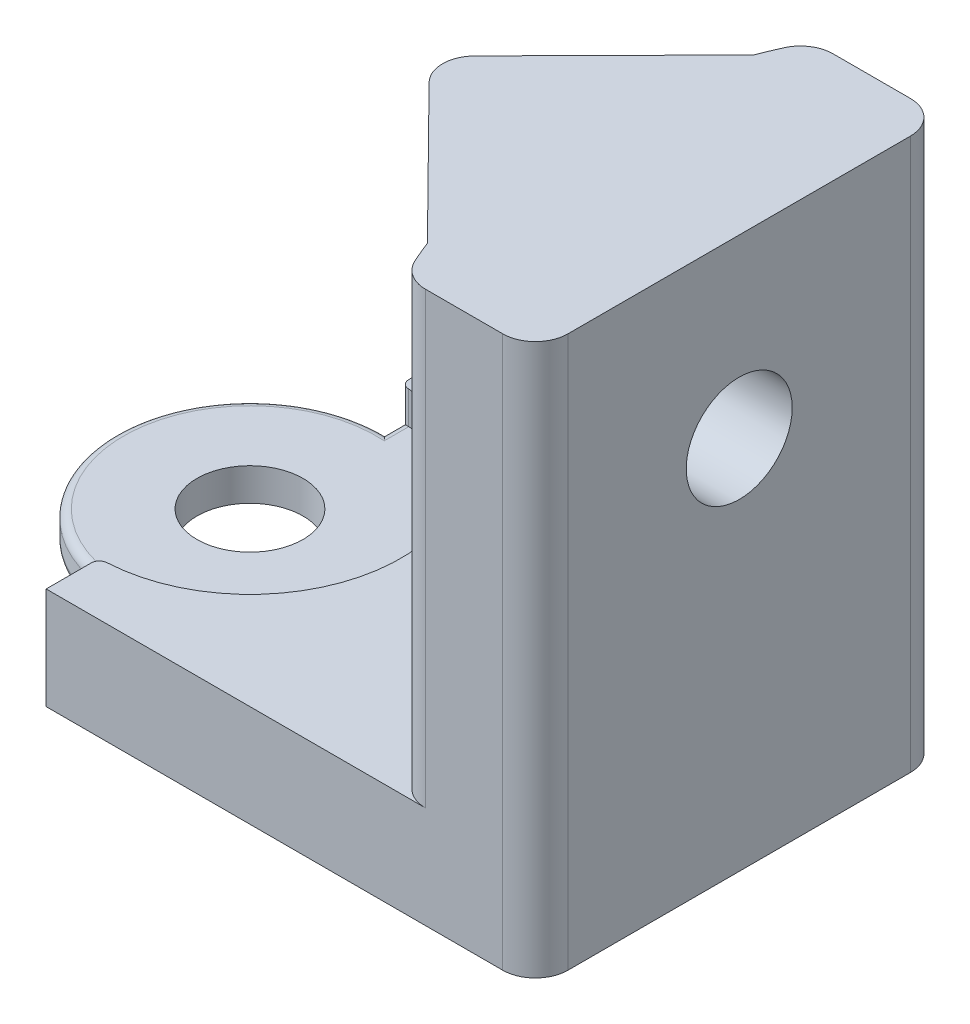
SolidWorks part; units mm, degrees
ref_plane "Front Plane" through (0, 0, 0) normal (0, 0, 1) x (1, 0, 0)
ref_plane "Top Plane" through (0, 0, 0) normal (0, 1, 0) x (1, 0, 0)
ref_plane "Right Plane" through (0, 0, 0) normal (1, 0, 0) x (0, 0, -1)
sketch "Sketch1" plane through (0, 0, 0) normal (0, 1, 0) x (1, 0, 0)
  line L0 (30, -12.5) -> (0, -12.5)
  line L1 (30, -12.5) -> (30, 12.5)
  line L2 (0, -12.5) -> (0, 12.5)
  line L3 (30, 12.5) -> (0, 12.5)
  line L4 (30, -12.5) -> (0, 12.5) construction
  line L5 (0, -12.5) -> (30, 12.5) construction
  line L6 (22, 12.5) -> (22, -12.5) construction
  circle A0 centre (0, 0) radius 3.25
  circle A1 centre (0, 0) radius 8.25
  arc A3 (0, -9.25) -> (0, 9.25) centre (0, 0) ccw
  arc A4 (22, -12.5) -> (22, 12.5) centre (46.5417, 0) cw
  point P5 (15, 0)
  point P15 (19, 0)
  dimension "D1" = 6.5
  dimension "D2" = 5
  dimension "D3" = 1
  dimension "D4" = 30
  dimension "D5" = 25
  dimension "D7" = 19
  dimension "D8" = 3
extrude "Boss-Extrude1" add sketch "Sketch1" along normal blind 2.25 contours L0 A4 L3 L2 A3 | A4 L0 L1 L3 region at (24.9493, 0, 0) region at (12.2478, 0, 0)
extrude "Boss-Extrude2" add sketch "Sketch1<4>" along normal blind 2 from surface contours L2 A3 A1 | L0 A4 L3 L2 A3 | A4 L0 L1 L3 | A1 | A0 region at (24.9493, 0, 0) region at (12.2478, 0, 0) region at (0.2068, 0, 8.75) starting at face at (11.5417, 2.25, 0)
sketch "Sketch1<4>" plane through (0, 0, 0) normal (0, 1, 0) x (1, 0, 0) same geometry as "Sketch1"
extrude "Boss-Extrude3" add sketch "Sketch1<6>" along normal blind 2 from surface contours L0 A4 L3 L2 A3 | A4 L0 L1 L3 region at (24.9493, 0, 0) region at (12.2478, 0, 0) starting at face at (8.625, 4.25, 0)
sketch "Sketch1<6>" plane through (0, 0, 0) normal (0, 1, 0) x (1, 0, 0) same geometry as "Sketch1"
extrude "Boss-Extrude6" add sketch "Sketch1<8>" along normal blind 33.8 contours A4 L0 L1 L3 region at (24.9493, 0, 0)
sketch "Sketch1<8>" plane through (0, 0, 0) normal (0, 1, 0) x (1, 0, 0) same geometry as "Sketch1"
sketch "Sketch3" plane through (0, 33.8, 0) normal (0, 1, 0) x (1, 0, 0)
  line L0 (19, 0) -> (11, 0) construction
  line L1 (11, 0) -> (20.8796, 10)
  line L2 (11, 0) -> (20.8796, -10)
  line L3 (22, -12.5) -> (30, -12.5)
  line L4 (30, -12.5) -> (30, 12.5)
  line L5 (30, 12.5) -> (22, 12.5)
  line L6 (22, -12.5) -> (30, -12.5)
  line L7 (30, -12.5) -> (30, 12.5)
  line L8 (30, 12.5) -> (22, 12.5)
  arc A0 (22, 12.5) -> (22, -12.5) centre (46.5417, 0) ccw construction
  arc A1 (22, 12.5) -> (22, -12.5) centre (46.5417, 0) ccw
  arc A2 (22, 12.5) -> (22, -12.5) centre (46.5417, 0) ccw
  arc M8 (22, 12.5) -> (22, -12.5) centre (46.5417, 0) ccw
  line M9 (22, -12.5) -> (30, -12.5)
  line M10 (30, -12.5) -> (30, 12.5)
  line M11 (30, 12.5) -> (22, 12.5)
  dimension "D2" = 8
  dimension "D3" = 20
  dimension "D1" = 0
extrude "Boss-Extrude7" add sketch "Sketch3" against normal blind 3.8 contours L0 L1 M8 | A2 L0 L2 | A2 M11 M8 M9 M10 region at (16.7152, 33.8, 3.1843) region at (16.7152, 33.8, -3.1843) region at (24.9493, 33.8, 0)
fillet "Fillet1" radius 2 1 edges at (11, 31.9, 0)
fillet "Fillet2" radius 2 4 edges at (30, 16.9, -12.5) (30, 16.9, 12.5) (22, 20.025, -12.5) (22, 20.025, 12.5)
fillet "Fillet3" radius 0.5 10 edges at (0, 2.25, -8.75) (-8.25, 2.25, 0) (0, 2.25, 8.75) (0, 4.25, 8.75) (-8.25, 4.25, 0) (0, 4.25, -8.75) (0, 5.25, 9.25) (0, 1.125, 9.25) (0, 1.125, -9.25) (0, 5.25, -9.25)
sketch "Sketch6" plane through (30, 0, 0) normal (1, 0, 0) x (0, 0, -1)
  line L0 (-10, 30) -> (10, 30) construction
  circle A0 centre (0, 23) radius 3.25
  dimension "D1" = 6.5
  dimension "D2" = 7
extrude "Cut-Extrude1" cut sketch "Sketch6" against normal up to next
